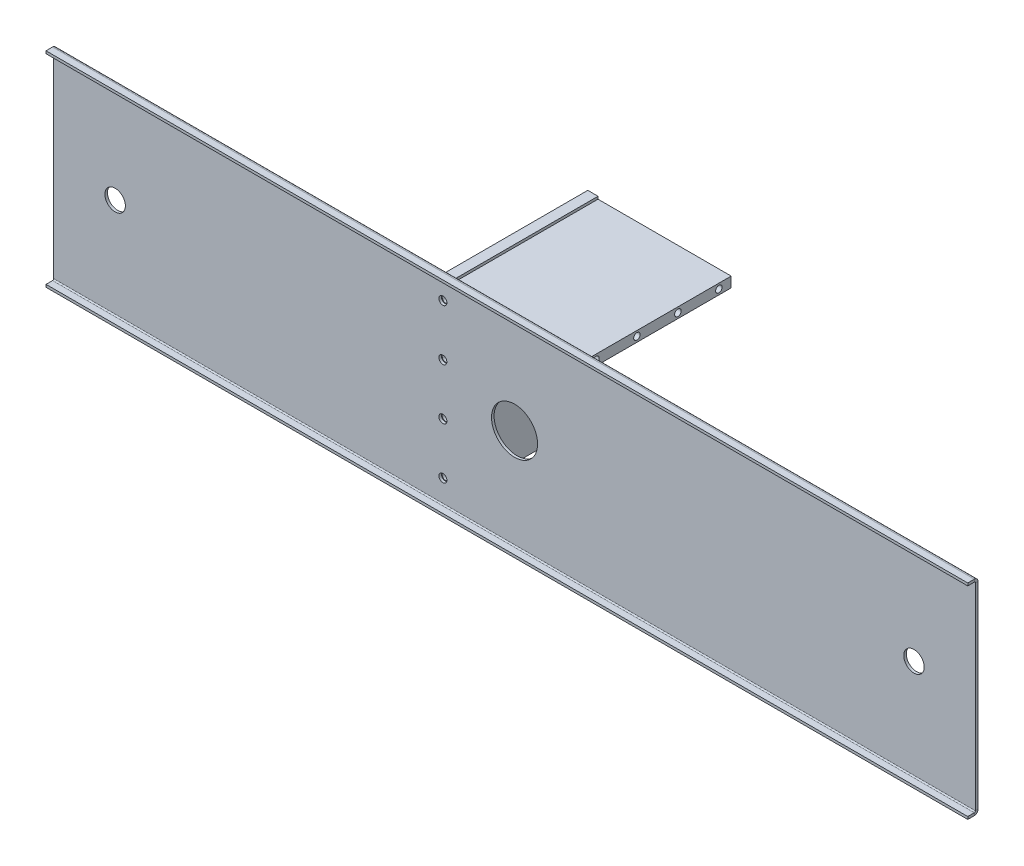
SolidWorks part; units mm, degrees
note: The reader was unsure of these and kept them because the rebuilt part matched: flange length of "Edge-Flange1", "Edge-Flange3".
ref_plane "Front Plane" through (0, 0, 0) normal (0, 0, 1) x (1, 0, 0)
ref_plane "Top Plane" through (0, 0, 0) normal (0, 1, 0) x (1, 0, 0)
ref_plane "Right Plane" through (0, 0, 0) normal (1, 0, 0) x (0, 0, -1)
sketch "Sketch1" plane through (0, 0, 0) normal (0, 0, 1) x (1, 0, 0)
  line L0 (-247.6416, 0) -> (247.6416, 0) construction
  line L2 (-21.0058, 57.15) -> (21.0058, 57.15) construction
  line L3 (-21.0058, 57.15) -> (-21.0058, 107.95)
  line L4 (-21.0058, 107.95) -> (21.0058, 107.95)
  line L5 (21.0058, 57.15) -> (21.0058, 107.95)
  line L6 (-25, 167.95) -> (25, 167.95)
  line L7 (-25, 167.95) -> (-25, 107.95)
  line L8 (-25, 107.95) -> (25, 107.95)
  line L9 (25, 167.95) -> (25, 107.95)
  line L10 (-9.7217, 27.2542) -> (9.7217, 27.2542)
  line L11 (-11.1125, 38.8874) -> (-11.1125, 50.8)
  line L13 (11.1125, 38.8874) -> (11.1125, 50.8)
  line L14 (-11.1125, 50.8) -> (11.1125, 50.8)
  line L15 (-11.1125, 38.8874) -> (-11.7729, 38.8874)
  line L16 (-11.7729, 38.8874) -> (-9.7217, 27.2542)
  line L17 (9.7217, 27.2542) -> (11.7729, 38.8874)
  line L18 (11.7729, 38.8874) -> (11.1125, 38.8874)
  line L19 (-247.6416, 36.3855) -> (0, 36.3855)
  line L20 (-247.6416, -36.3855) -> (0, -36.3855)
  circle A0 centre (-247.6416, 0) radius 196.85
  circle A2 centre (247.6416, 0) radius 196.85
  circle A3 centre (0, 0) radius 38.354
  circle A4 centre (-247.6416, 0) radius 36.3855 construction
  circle A5 centre (0, 0) radius 36.3855 construction
  circle A6 centre (247.6416, 0) radius 36.3855 construction
  arc A7 (-247.6416, 36.3855) -> (-247.6416, -36.3855) centre (-247.6416, 0) ccw
  arc A8 (0, 36.3855) -> (0, -36.3855) centre (0, 0) cw
  point P9 (0, 57.15)
  point P10 (0, 107.95)
  point P17 (0, 27.2542)
  point P24 (0, 50.8)
  point P36 (0, 0)
  point P37 (0, 0)
  point P38 (0, 0)
  dimension "D1" = 495.2832
  dimension "D6" = 76.708
  dimension "D7" = 393.7
  dimension "D14" = 72.771
  dimension "D15" = 723.9
  dimension "D2" = 42.0116
  dimension "D3" = 50.8
  dimension "D4" = 50
  dimension "D5" = 60
  dimension "D8" = 23.5458
  dimension "D9" = 50.8
  dimension "D10" = 22.225
  dimension "D11" = 11.9126
  dimension "D12" = 23.5458
  dimension "D13" = 20
  dimension "D16" = 6.35
ref_plane "Plane1" through (0, 0, 45.72) normal (0, 0, 1) x (1, 0, 0)
sketch "Sketch2" plane through (0, 0, 45.72) normal (0, 0, 1) x (1, 0, 0)
  line L0 (-247.6416, 0) -> (247.6416, 0) construction
  line L1 (-285.75, 63.5) -> (285.75, 63.5)
  line L2 (-285.75, 63.5) -> (-285.75, -63.5)
  line L3 (-285.75, -63.5) -> (285.75, -63.5)
  line L4 (285.75, 63.5) -> (285.75, -63.5)
  circle A0 centre (-247.6416, 0) radius 6.35
  circle A1 centre (0, 0) radius 14.2875
  circle A2 centre (247.6416, 0) radius 6.35
  circle A3 centre (-247.6416, 0) radius 36.3855 construction
  circle A4 centre (247.6416, 0) radius 36.3855 construction
  point P15 (-285.75, 0)
  point P18 (0, 63.5)
  dimension "D1" = 12.7
  dimension "D2" = 28.575
  dimension "D3" = 127
  dimension "D4" = 571.5
base flange "Base-Flange1" sketch "Sketch2" thickness 1.5875 reverse thickness direction yes parameters "D1"=0.7366
edge flange "Edge-Flange1" sketch "Sketch21" flange angle 90 flange length 6.35 flange position material inside bend radius 0.7366 thickness 1.5875 relief rectangular parameters "D6"=10
bend "EdgeBend4" bend radius 0.7366 bend angle 90 parameters "D5"=1
sketch "Sketch21" plane through (0, 63.5, 47.3075) normal (0, 1, 0) x (-1, 0, 0)
  line L0 (-285.75, 0) -> (285.75, 0) construction
  line L1 (-285.75, 0) -> (285.75, 0)
  line L2 (-285.75, 0) -> (-285.75, 4.7625)
  line L3 (-285.75, 4.7625) -> (285.75, 4.7625)
  line L4 (285.75, 4.7625) -> (285.75, 0)
edge flange "Edge-Flange3" sketch "Sketch23" flange angle 90 flange length 6.35 flange position material inside bend radius 0.7366 thickness 1.5875 relief rectangular parameters "D6"=10
bend "EdgeBend5" bend radius 0.7366 bend angle 90 parameters "D5"=2
sketch "Sketch23" plane through (0, -63.5, 47.3075) normal (0, -1, 0) x (1, 0, 0)
  line L0 (-285.75, 0) -> (285.75, 0) construction
  line L1 (-285.75, 0) -> (285.75, 0)
  line L2 (-285.75, 0) -> (-285.75, 4.7625)
  line L3 (-285.75, 4.7625) -> (285.75, 4.7625)
  line L4 (285.75, 4.7625) -> (285.75, 0)
sketch "Sketch16" plane through (0, 0, 45.72) normal (0, 0, -1) x (-1, 0, 0)
  line L0 (261.3897, 7.9375) -> (233.8934, -7.9375) construction
  line L1 (247.6416, 0) -> (-247.6416, 0) construction
  line L2 (233.8934, -7.9375) -> (233.8934, 0) construction
  line L3 (-233.8934, -7.9375) -> (-261.3897, 7.9375) construction
  line L4 (-261.3897, 7.9375) -> (-261.3897, 0) construction
  circle A6 centre (261.3897, 7.9375) radius 2.4892 construction
  circle A7 centre (233.8934, -7.9375) radius 2.4892 construction
  circle A8 centre (247.6416, 0) radius 6.35 construction
  circle A9 centre (-247.6416, 0) radius 6.35 construction
  circle A10 centre (-261.3897, 7.9375) radius 2.4892 construction
  circle A11 centre (-233.8934, -7.9375) radius 2.4892 construction
  point P3 (247.6416, 0)
  point P7 (-247.6416, 0)
  dimension "D3" = 31.75
  dimension "D4" = 4.9784
  dimension "D5" = 4.9784
  dimension "D6" = 30
sketch "Sketch18" plane through (0, 0, 0) normal (0, 0, 1) x (1, 0, 0)
  line L1 (-47.625, 58.7375) -> (-41.275, 58.7375)
  line L2 (-47.625, 58.7375) -> (-47.625, -58.7375)
  line L3 (-47.625, -58.7375) -> (-41.275, -58.7375)
  line L4 (-41.275, 58.7375) -> (-41.275, -58.7375)
  point P4 (-41.275, 0)
  dimension "D1" = 117.475
  dimension "D2" = 6.35
  dimension "D3" = 41.275
extrude "Boss-Extrude1" add sketch "Sketch18" along normal mid plane 91.44 separate body
sketch "Sketch24" plane through (-41.275, 0, 0) normal (1, 0, 0) x (0, 0, -1)
  line L0 (-45.72, -58.7375) -> (-45.72, 58.7375) construction
  line L1 (-45.72, 38.9255) -> (-29.845, 38.9255)
  line L2 (-45.72, 38.9255) -> (-45.72, 26.2255)
  line L3 (-45.72, 26.2255) -> (-29.845, 26.2255)
  line L4 (-29.845, 38.9255) -> (-29.845, 26.2255)
  line L5 (-37.7825, 26.2255) -> (-37.7825, -26.2255) construction
  line L6 (-45.72, -38.9255) -> (-29.845, -38.9255)
  line L7 (-45.72, -38.9255) -> (-45.72, -26.2255)
  line L8 (-45.72, -26.2255) -> (-29.845, -26.2255)
  line L9 (-29.845, -38.9255) -> (-29.845, -26.2255)
  point P13 (-37.7825, 0)
  dimension "D1" = 12.7
  dimension "D2" = 15.875
  dimension "D3" = 2.54
extrude "Cut-Extrude1" cut sketch "Sketch24" against normal up to next (6.35 mm away)
sketch "Sketch25" plane through (0, 0, 47.3075) normal (0, 0, 1) x (1, 0, 0)
  line L0 (-44.45, 47.625) -> (-44.45, 15.875) construction
  line L1 (-44.45, 15.875) -> (-44.45, -15.875) construction
  line L2 (-44.45, -15.875) -> (-44.45, -47.625) construction
  line L3 (-41.275, 58.7375) -> (-47.625, 58.7375) construction
  line L4 (-41.275, 58.7375) -> (-47.625, 58.7375) construction
  circle A0 centre (-44.45, 47.625) radius 2.4892
  circle A1 centre (-44.45, 15.875) radius 2.4892
  circle A2 centre (-44.45, -15.875) radius 2.4892
  circle A3 centre (-44.45, -47.625) radius 2.4892
  point P8 (-44.45, 0)
  point P12 (-44.45, 58.7375)
  dimension "D1" = 4.9784
  dimension "D2" = 31.75
extrude "Cut-Extrude2" cut sketch "Sketch25" against normal up to next (1.5875 mm away)
hole_wizard "#10-32 Tapped Hole1" positions "Sketch26" profile "Sketch28" tap size "#10-32" standard "ANSI Inch"
sketch "Sketch26" plane through (0, 0, 45.72) normal (0, 0, 1) x (1, 0, 0)
  circle A0 centre (-44.45, 15.875) radius 2.4892 construction
  circle A1 centre (-44.45, 47.625) radius 2.4892 construction
  point P0 (-44.45, 47.625)
  point P2 (-44.45, 15.875)
  point P4 (-44.45, -15.875)
  point P7 (-44.45, -47.625)
  point P11 (0, 0)
sketch "Sketch28" plane through (-44.45, 47.625, 45.72) normal (1, 0, 0) x (0, -1, 0)
  line L0 (0, 0) -> (0, 13.9133)
  line L1 (0, 13.9133) -> (2.0193, 12.7)
  line L2 (2.0193, 12.7) -> (2.0193, 0)
  line L5 (2.0193, 0) -> (0, 0)
  line L10 (0, 13.9133) -> (-2.0193, 12.7) construction
  line L11 (0, -6.35) -> (0, 107.95) construction
  dimension "Tap Drill Dia." = 4.0386
  dimension "Tap Drill Depth" = 12.7
  dimension "Drill Angle" = 118
cosmetic thread "Hole Thread1"
cosmetic thread "Hole Thread2"
cosmetic thread "Hole Thread3"
cosmetic thread "Hole Thread4"
sketch "Sketch29" plane through (-41.275, 0, 0) normal (1, 0, 0) x (0, 0, -1)
  line L0 (-45.72, 38.9255) -> (-45.72, 58.7375) construction
  line L1 (-45.72, 57.15) -> (45.72, 57.15)
  line L2 (-45.72, 57.15) -> (-45.72, 50.8)
  line L3 (-45.72, 50.8) -> (45.72, 50.8)
  line L4 (45.72, 57.15) -> (45.72, 50.8)
  line L5 (45.72, -58.7375) -> (45.72, 58.7375) construction
extrude "Boss-Extrude2" add sketch "Sketch29" along normal blind 82.55 separate body
sketch "Sketch32" plane through (-47.625, 0, 0) normal (-1, 0, 0) x (0, 0, 1)
  line L0 (-38.1, 53.975) -> (-12.7, 53.975) construction
  line L1 (-12.7, 53.975) -> (12.7, 53.975) construction
  line L2 (12.7, 53.975) -> (38.1, 53.975) construction
  line L3 (-45.72, 50.8) -> (-45.72, 57.15) construction
  circle A0 centre (-38.1, 53.975) radius 2.4892
  circle A1 centre (-12.7, 53.975) radius 2.4892
  circle A2 centre (12.7, 53.975) radius 2.4892
  circle A3 centre (38.1, 53.975) radius 2.4892
  point P8 (0, 53.975)
  point P9 (0, 0)
  point P13 (-45.72, 53.975)
  dimension "D1" = 4.9784
  dimension "D2" = 25.4
extrude "Cut-Extrude3" cut sketch "Sketch32" against normal up to next (6.35 mm away)
hole_wizard "#10-32 Tapped Hole2" positions "Sketch33" profile "Sketch34" tap size "#10-32" standard "ANSI Inch"
sketch "Sketch33" plane through (-41.275, 0, 0) normal (-1, 0, 0) x (0, 0, 1)
  point P0 (-38.1, 53.975)
  point P3 (-12.7, 53.975)
  point P6 (12.7, 53.975)
  point P9 (38.1, 53.975)
sketch "Sketch34" plane through (-41.275, 53.975, -38.1) normal (0, 1, 0) x (0, 0, 1)
  line L0 (0, 0) -> (0, 13.9133)
  line L1 (0, 13.9133) -> (2.0193, 12.7)
  line L2 (2.0193, 12.7) -> (2.0193, 0)
  line L5 (2.0193, 0) -> (0, 0)
  line L10 (0, 13.9133) -> (-2.0193, 12.7) construction
  line L11 (0, -6.35) -> (0, 107.95) construction
  dimension "Tap Drill Dia." = 4.0386
  dimension "Tap Drill Depth" = 12.7
  dimension "Drill Angle" = 118
cosmetic thread "Hole Thread5"
cosmetic thread "Hole Thread6"
cosmetic thread "Hole Thread7"
cosmetic thread "Hole Thread8"
mirror "Mirror1" about plane through (0, 0, 0) normal (1, 0, 0) of "#10-32 Tapped Hole2"
cosmetic thread "Hole Thread9"
cosmetic thread "Hole Thread10"
cosmetic thread "Hole Thread11"
cosmetic thread "Hole Thread12"
mirror "Mirror2" about plane through (0, 0, 0) normal (0, 0, 1) of "#10-32 Tapped Hole1"
cosmetic thread "Hole Thread13"
cosmetic thread "Hole Thread14"
cosmetic thread "Hole Thread15"
cosmetic thread "Hole Thread16"
sketch "Bend-Lines1" [suppressed] plane through (0, 0, 0) normal (0, 1, 0) x (1, 0, 0)
sketch "Bounding-Box1" [suppressed] plane through (0, 0, 0) normal (0, 1, 0) x (1, 0, 0)
sheet metal parameters "Sheet-Metal1" thickness 1.5875 parameters "D1"=0.7366
flat pattern "Flat-Pattern1" [suppressed]
sketch "Bend-Lines2" plane through (0, 0, 0) normal (0, 1, 0) x (1, 0, 0)
sketch3d "Bounding-Box2" [suppressed]
  line L0 (285.75, -63.5, 0) -> (-285.75, -63.5, 0) construction
  line L1 (285.75, 63.5, 0) -> (-285.75, 63.5, 0) construction
  line L2 (285.75, -63.5, 0) -> (285.75, 63.5, 0) construction
  line L3 (-285.75, -63.5, 0) -> (-285.75, 63.5, 0) construction
sheet metal parameters "Sheet-Metal2" thickness 1.5875 parameters "D1"=0.7366
flat pattern "Flat-Pattern1" [suppressed]
sketch "Bend-Lines2" plane through (0, 0, 45.72) normal (0, 0, 1) x (1, 0, 0)
  line L0 (285.75, 62.3778) -> (-285.75, 62.3778) construction
  line L1 (285.75, 62.3778) -> (-285.75, 62.3778) construction
sketch3d "Bounding-Box2" [suppressed]
  line L0 (-285.75, -63.5, 0) -> (285.75, -63.5, 0) construction
  line L1 (-285.75, 67.6057, 0) -> (285.75, 67.6057, 0) construction
  line L2 (-285.75, -63.5, 0) -> (-285.75, 67.6057, 0) construction
  line L3 (285.75, -63.5, 0) -> (285.75, 67.6057, 0) construction
bend of the flat pattern "Flatten-<EdgeBend4>1"
sheet metal parameters "Sheet-Metal4" thickness 1.5875 parameters "D1"=0.7366
flat pattern "Flat-Pattern1"
sketch "Bend-Lines2" plane through (0, 0, 45.72) normal (0, 0, -1) x (-1, 0, 0)
  line L0 (-285.75, -62.3778) -> (285.75, -62.3778) construction
  line L1 (-285.75, -62.3778) -> (285.75, -62.3778) construction
  line L2 (285.75, 62.3778) -> (-285.75, 62.3778) construction
  line L3 (285.75, 62.3778) -> (-285.75, 62.3778) construction
sketch3d "Bounding-Box2" [suppressed]
  line L0 (285.75, -67.6057, 0) -> (-285.75, -67.6057, 0) construction
  line L1 (285.75, 67.6057, 0) -> (-285.75, 67.6057, 0) construction
  line L2 (285.75, -67.6057, 0) -> (285.75, 67.6057, 0) construction
  line L3 (-285.75, -67.6057, 0) -> (-285.75, 67.6057, 0) construction
bend of the flat pattern "Flatten-<EdgeBend4>2"
bend of the flat pattern "Flatten-<EdgeBend5>1"
sheet metal parameters "Sheet-Metal7" thickness 1.5875 parameters "D1"=0.7366
flat pattern "Flat-Pattern1"
sketch "Bend-Lines2" plane through (0, 0, 45.72) normal (0, 0, -1) x (-1, 0, 0)
  line L0 (-285.75, -62.3778) -> (285.75, -62.3778) construction
  line L1 (-285.75, -62.3778) -> (285.75, -62.3778) construction
  line L2 (285.75, 62.3778) -> (-285.75, 62.3778) construction
  line L3 (285.75, 62.3778) -> (-285.75, 62.3778) construction
sketch3d "Bounding-Box2" [suppressed]
  line L0 (285.75, -67.6057, 0) -> (-285.75, -67.6057, 0) construction
  line L1 (285.75, 67.6057, 0) -> (-285.75, 67.6057, 0) construction
  line L2 (285.75, -67.6057, 0) -> (285.75, 67.6057, 0) construction
  line L3 (-285.75, -67.6057, 0) -> (-285.75, 67.6057, 0) construction
bend of the flat pattern "Flatten-<EdgeBend4>2"
bend of the flat pattern "Flatten-<EdgeBend5>1"
sheet metal parameters "Sheet-Metal9" thickness 1.5875 parameters "D1"=0.7366
flat pattern "Flat-Pattern9"
sketch "Bend-Lines3" plane through (0, 0, 45.72) normal (0, 0, -1) x (-1, 0, 0)
  line L0 (-285.75, -62.3778) -> (285.75, -62.3778) construction
  line L1 (285.75, 62.3778) -> (-285.75, 62.3778) construction
  line L2 (-285.75, -62.3778) -> (285.75, -62.3778) construction
  line L3 (285.75, 62.3778) -> (-285.75, 62.3778) construction
sketch3d "Bounding-Box3" [suppressed]
  line L0 (285.75, -67.6057, 0) -> (-285.75, -67.6057, 0) construction
  line L1 (285.75, 67.6057, 0) -> (-285.75, 67.6057, 0) construction
  line L2 (285.75, -67.6057, 0) -> (285.75, 67.6057, 0) construction
  line L3 (-285.75, -67.6057, 0) -> (-285.75, 67.6057, 0) construction
bend of the flat pattern "Flatten-<EdgeBend5>2"
bend of the flat pattern "Flatten-<EdgeBend4>3"
